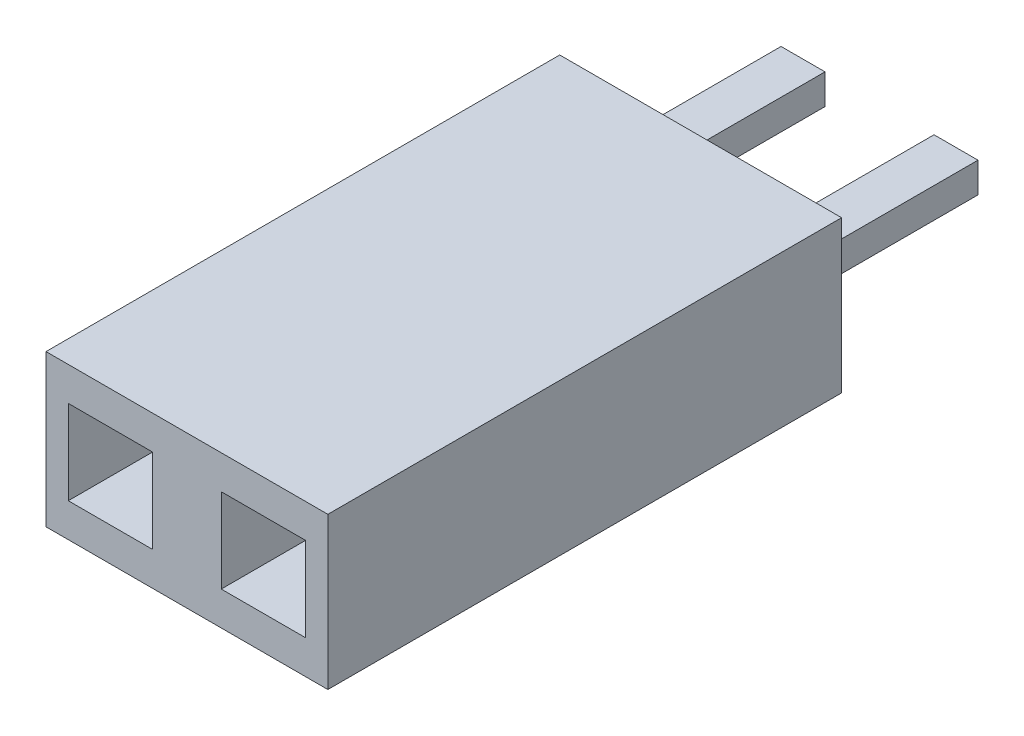
SolidWorks part; units mm, degrees
ref_plane "Front" through (0, 0, 0) normal (0, 0, 1) x (1, 0, 0)
ref_plane "Top" through (0, 0, 0) normal (0, 1, 0) x (1, 0, 0)
ref_plane "Right" through (0, 0, 0) normal (1, 0, 0) x (0, 0, -1)
sketch "Sketch1" plane through (0, 0, 0) normal (0, 0, 1) x (1, 0, 0)
  line L0 (-5.3495, 1.2024) -> (-0.6695, 1.2024)
  line L1 (-0.6695, 1.2024) -> (-0.6695, -1.3176)
  line L2 (-0.6695, -1.3176) -> (-5.3495, -1.3176)
  line L3 (-5.3495, -1.3176) -> (-5.3495, 1.2024)
  dimension "D1" = 4.68
  dimension "D2" = 2.52
extrude "Component_Outline" add sketch "Sketch1" along normal blind 8.53 separate body
sketch3d "3DSketch1"
  line L0 (0, 0, 0) -> (1, 0, 0)
  line L1 (0, 0, 0) -> (0, 1, 0)
  line L2 (0, 0, 0) -> (0, 0, 1)
  point P0 (0, 0, 0)
sketch "Sketch2" plane through (0, 0, 8.53) normal (0, 0, 1) x (1, 0, 0)
  line L0 (-5.3495, -0.0576) -> (-0.6695, -0.0576) construction
  line L1 (-5.3495, 1.2024) -> (-5.3495, -1.3176) construction
  line L2 (-0.6695, -1.3176) -> (-0.6695, 1.2024) construction
  line L4 (-1.0395, -0.7576) -> (-2.4395, -0.7576)
  line L5 (-1.0395, -0.7576) -> (-1.0395, 0.6424)
  line L6 (-1.0395, 0.6424) -> (-2.4395, 0.6424)
  line L7 (-2.4395, -0.7576) -> (-2.4395, 0.6424)
  line L8 (-1.0395, -0.7576) -> (-2.4395, 0.6424) construction
  line L9 (-1.0395, 0.6424) -> (-2.4395, -0.7576) construction
  point P6 (-1.7395, -0.0576)
  dimension "D1" = 1.4
  dimension "D2" = 1.4
  dimension "D3" = 0.37
extrude "Cut-Extrude1" cut sketch "Sketch2" against normal blind 8
pattern_linear "LPattern1" count 2 spacing 2.54 along (-1, 0, 0) of "Cut-Extrude1"
sketch "Sketch3" plane through (0, 0, 0.53) normal (0, 0, 1) x (1, 0, 0)
  line L0 (-1.7395, 0.6424) -> (-1.7395, -0.7576) construction
  line L1 (-1.0395, 0.6424) -> (-2.4395, 0.6424) construction
  line L2 (-2.4395, -0.7576) -> (-1.0395, -0.7576) construction
  line L6 (-1.3745, -0.3076) -> (-2.1045, -0.3076)
  line L7 (-1.3745, -0.3076) -> (-1.3745, 0.1924)
  line L8 (-1.3745, 0.1924) -> (-2.1045, 0.1924)
  line L9 (-2.1045, -0.3076) -> (-2.1045, 0.1924)
  line L10 (-1.3745, -0.3076) -> (-2.1045, 0.1924) construction
  line L11 (-1.3745, 0.1924) -> (-2.1045, -0.3076) construction
  point P8 (-1.7395, -0.0576)
  dimension "D1" = 0.73
  dimension "D2" = 0.5
extrude "Boss-Extrude1" add sketch "Sketch3" against normal blind 3.5
pattern_linear "LPattern2" count 2 spacing 2.54 along (-1, 0, 0) of "Boss-Extrude1"
sketch "Sketch4" plane through (0, 0, -2.97) normal (0, 0, -1) x (-1, 0, 0)
  line L0 (4.6445, 0.1924) -> (3.9145, -0.3076) construction
  line L2 (2.1045, 0.1924) -> (1.3745, -0.3076) construction
  point P6 (1.7395, -0.0576)
  point P9 (4.2795, -0.0576)
ref_axis "Axis1" through (-4.2795, -0.0576, 0.3664) along (0, 0, -1)
ref_axis "Axis2" through (-1.7395, -0.0576, 0.0216) along (0, 0, -1)
